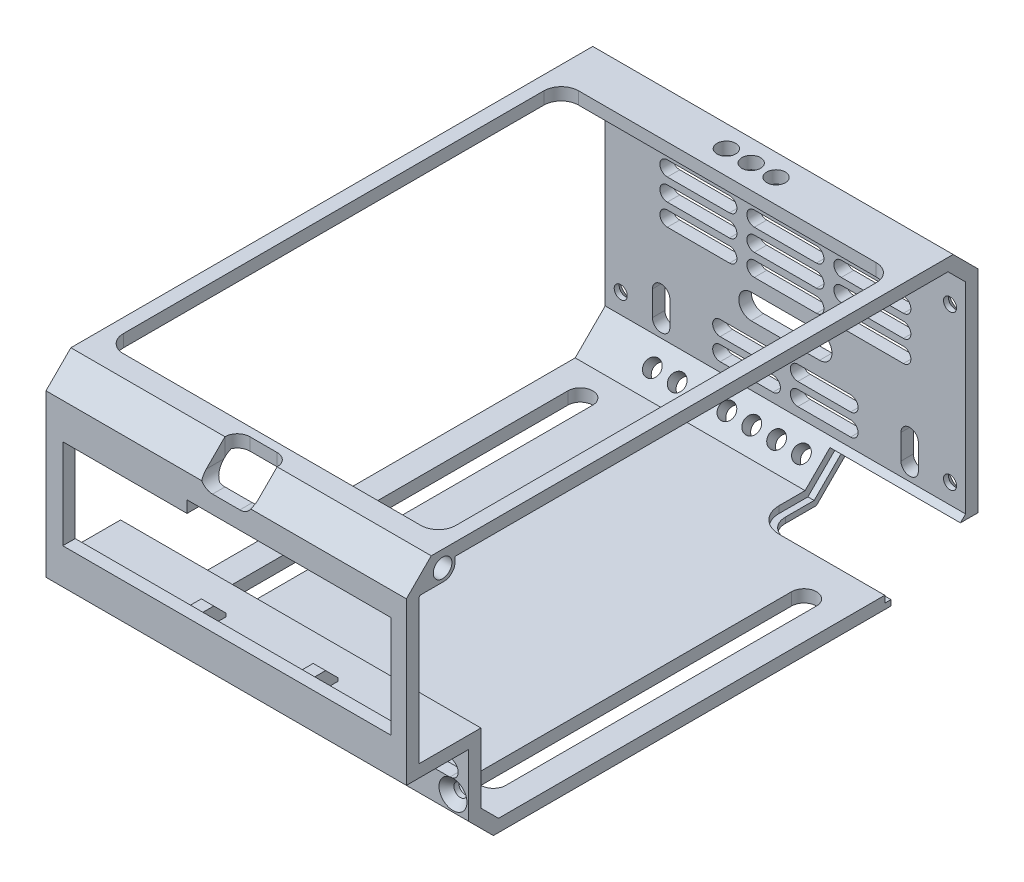
SolidWorks part; units mm, degrees
ref_plane "前视基准面" through (0, 0, 0) normal (0, 0, 1) x (1, 0, 0)
ref_plane "上视基准面" through (0, 0, 0) normal (0, 1, 0) x (1, 0, 0)
ref_plane "右视基准面" through (0, 0, 0) normal (1, 0, 0) x (0, 0, -1)
other "Configuration Table"
sketch "草图1" plane through (0, 0, 0) normal (0, 1, 0) x (1, 0, 0)
  line L1 (-28.831, 36.5169) -> (29.169, 36.5169)
  line L2 (-28.831, 36.5169) -> (-28.831, -55.4831)
  line L3 (-28.831, -55.4831) -> (29.169, -55.4831)
  line L4 (29.169, 36.5169) -> (29.169, -55.4831)
  dimension "D1" = 58
  dimension "D2" = 92
extrude "凸台-拉伸1" add sketch "草图1" along normal blind 44
sketch "草图2" plane through (-28.831, 0, 0) normal (-1, 0, 0) x (0, 0, 1)
  line L0 (55.4831, 44) -> (55.4831, 0) construction
  line L1 (55.4831, 14) -> (45.4831, 14)
  line L2 (55.4831, 14) -> (55.4831, 0)
  line L3 (55.4831, 0) -> (45.4831, 0)
  line L4 (45.4831, 14) -> (45.4831, 0)
  line L5 (-36.5169, 0) -> (55.4831, 0) construction
  dimension "D1" = 14
  dimension "D2" = 10
extrude "切除-拉伸1" cut sketch "草图2" against normal through all
chamfer "倒角1" distance 4 angle 45 3 edges at (0.169, 44, 55.4831) (0.169, 44, -36.5169) (0.169, 0, 45.4831)
chamfer "倒角2" distance 6 angle 45 1 edges at (0.169, 0, -36.5169)
sketch "草图3" plane through (-28.831, 0, 0) normal (-1, 0, 0) x (0, 0, 1)
  line L20 (-34.5169, 39.1716) -> (-34.5169, 6.8284)
  line L21 (-34.5169, 6.8284) -> (-29.6885, 2)
  line L22 (-29.6885, 2) -> (40.6547, 2)
  line L23 (40.6547, 2) -> (43.4831, 4.8284)
  line L24 (43.4831, 4.8284) -> (43.4831, 16)
  line L25 (43.4831, 16) -> (53.4831, 16)
  line L26 (53.4831, 16) -> (53.4831, 39.1716)
  line L27 (53.4831, 39.1716) -> (50.6547, 42)
  line L28 (50.6547, 42) -> (-31.6885, 42)
  line L29 (-31.6885, 42) -> (-34.5169, 39.1716)
  line L30 (-34.5169, 39.1716) -> (-34.5169, 6.8284)
  line L31 (-34.5169, 6.8284) -> (-29.6885, 2)
  line L32 (-29.6885, 2) -> (40.6547, 2)
  line L33 (40.6547, 2) -> (43.4831, 4.8284)
  line L34 (43.4831, 4.8284) -> (43.4831, 16)
  line L35 (43.4831, 16) -> (53.4831, 16)
  line L36 (53.4831, 16) -> (53.4831, 39.1716)
  line L37 (53.4831, 39.1716) -> (50.6547, 42)
  line L38 (50.6547, 42) -> (-31.6885, 42)
  line L39 (-31.6885, 42) -> (-34.5169, 39.1716)
  dimension "D1" = 2
extrude "切除-拉伸2" cut sketch "草图3" against normal through all
sketch "草图4" plane through (0, 0, 55.4831) normal (0, 0, 1) x (1, 0, 0)
  line L0 (26.669, 36.15) -> (-6.131, 36.15)
  line L2 (26.669, 36.15) -> (26.669, 19.75)
  line L3 (26.669, 19.75) -> (-26.131, 19.75)
  line L4 (-26.131, 34.25) -> (-26.131, 19.75)
  line L5 (-6.131, 36.15) -> (-6.131, 34.25)
  line L6 (-6.131, 34.25) -> (-26.131, 34.25)
  line L7 (29.169, 40) -> (29.169, 14) construction
  line L8 (-28.831, 44) -> (29.169, 44) construction
  dimension "D1" = 2.5
  dimension "D2" = 7.85
  dimension "D3" = 16.4
  dimension "D4" = 32.8
  dimension "D5" = 1.9
  dimension "D6" = 20
extrude "切除-拉伸3" cut sketch "草图4" against normal up to next
sketch "草图6" plane through (0, 44, 0) normal (0, 1, 0) x (1, 0, 0)
  line L0 (29.169, -51.4831) -> (29.169, 32.5169) construction
  line L1 (24.119, -48.0831) -> (-23.781, -48.0831)
  line L2 (26.919, -45.2831) -> (26.919, 22.3885)
  line L3 (24.119, 25.1885) -> (-23.781, 25.1885)
  line L4 (-26.581, -45.2831) -> (-26.581, 22.3885)
  line L5 (-28.831, 32.5169) -> (-28.831, -51.4831) construction
  line L6 (29.169, -55.4831) -> (-28.831, -55.4831) construction
  line L7 (29.169, 29.6885) -> (-28.831, 29.6885) construction
  arc A0 (-23.781, 25.1885) -> (-26.581, 22.3885) centre (-23.781, 22.3885) ccw
  arc A1 (-23.781, -48.0831) -> (-26.581, -45.2831) centre (-23.781, -45.2831) cw
  arc A2 (24.119, -48.0831) -> (26.919, -45.2831) centre (24.119, -45.2831) ccw
  arc A3 (26.919, 22.3885) -> (24.119, 25.1885) centre (24.119, 22.3885) ccw
  point P16 (-26.581, -48.0831)
  point P19 (26.919, -48.0831)
  point P22 (26.919, 25.1885)
  dimension "D5" = 2.8
  dimension "D1" = 2.25
  dimension "D2" = 2.25
  dimension "D3" = 7.4
  dimension "D4" = 4.5
extrude "切除-拉伸4" cut sketch "草图6" against normal up to next
sketch "草图7" plane through (0, 44, 0) normal (0, 1, 0) x (1, 0, 0)
  line L0 (29.169, -55.4831) -> (-28.831, -55.4831) construction
  line L1 (4.369, -55.4831) -> (-4.031, -55.4831)
  line L2 (4.369, -55.4831) -> (4.369, -49.4831)
  line L3 (4.369, -49.4831) -> (-4.031, -49.4831)
  line L4 (-4.031, -55.4831) -> (-4.031, -49.4831)
  point P6 (0.169, -55.4831)
  point P7 (0.169, -49.4831)
  dimension "D1" = 8.4
  dimension "D2" = 6
extrude "切除-拉伸5" cut sketch "草图7" against normal blind 5
fillet "圆角1" radius 2 4 edges at (-4.031, 39, 54.4831) (4.369, 39, 54.4831) (-4.031, 43, 49.4831) (4.369, 43, 49.4831)
sketch "草图8" plane through (0, 44, 0) normal (0, 1, 0) x (1, 0, 0)
  line L0 (-28.831, 36.5169) -> (29.169, 36.5169) construction
  circle A0 centre (4.169, 29.0169) radius 1.5
  circle A1 centre (0.169, 29.0169) radius 1.5
  circle A2 centre (-3.831, 29.0169) radius 1.5
  point P8 (0.169, 36.5169)
  dimension "D1" = 3
  dimension "D2" = 4
  dimension "D3" = 4
  dimension "D4" = 7.5
extrude "切除-拉伸6" cut sketch "草图8" against normal up to next
sketch "草图9" plane through (0, 16, 0) normal (0, 1, 0) x (1, 0, 0)
  line L0 (26.669, -53.4831) -> (-26.131, -53.4831) construction
  line L1 (11.169, -53.4831) -> (9.169, -53.4831)
  line L2 (11.169, -53.4831) -> (11.169, -48.4831)
  line L3 (11.169, -48.4831) -> (9.169, -48.4831)
  line L4 (9.169, -53.4831) -> (9.169, -48.4831)
  line L7 (-6.831, -53.4831) -> (-8.831, -53.4831)
  line L8 (-6.831, -53.4831) -> (-6.831, -48.4831)
  line L9 (-6.831, -48.4831) -> (-8.831, -48.4831)
  line L10 (-8.831, -53.4831) -> (-8.831, -48.4831)
  line L11 (29.169, -43.4831) -> (29.169, -53.4831) construction
  line L12 (-28.831, -43.4831) -> (-28.831, -53.4831) construction
  dimension "D1" = 2
  dimension "D2" = 2
  dimension "D3" = 18
  dimension "D4" = 20
  dimension "D5" = 5
extrude "凸台-拉伸2" add sketch "草图9" along normal blind 2.5
chamfer "倒角4" distance 2 angle 45 1 edges at (10.169, 18.5, 48.4831)
chamfer "倒角5" distance 2 angle 45 1 edges at (-7.831, 18.5, 48.4831)
sketch "草图10" plane through (0, 42, 0) normal (0, -1, 0) x (-1, 0, 0)
  line L0 (26.131, -53.4831) -> (6.131, -53.4831) construction
  line L1 (18.831, -53.4831) -> (20.831, -53.4831)
  line L2 (18.831, -53.4831) -> (18.831, -49.4831)
  line L3 (18.831, -49.4831) -> (20.831, -49.4831)
  line L4 (20.831, -53.4831) -> (20.831, -49.4831)
  line L5 (6.131, -53.4831) -> (-26.669, -53.4831) construction
  line L6 (-21.169, -53.4831) -> (-19.169, -53.4831)
  line L7 (-21.169, -53.4831) -> (-21.169, -49.4831)
  line L8 (-21.169, -49.4831) -> (-19.169, -49.4831)
  line L9 (-19.169, -53.4831) -> (-19.169, -49.4831)
  line L10 (-29.169, 34.5169) -> (28.831, 34.5169) construction
  line L11 (-13.169, 34.5169) -> (-11.169, 34.5169)
  line L12 (-13.169, 34.5169) -> (-13.169, 29.5169)
  line L13 (-13.169, 29.5169) -> (-11.169, 29.5169)
  line L14 (-11.169, 34.5169) -> (-11.169, 29.5169)
  line L15 (-29.169, -50.6547) -> (-29.169, 31.6885) construction
  line L16 (10.831, 34.5169) -> (12.831, 34.5169)
  line L17 (10.831, 34.5169) -> (10.831, 29.5169)
  line L18 (10.831, 29.5169) -> (12.831, 29.5169)
  line L19 (12.831, 34.5169) -> (12.831, 29.5169)
  line L20 (28.831, -50.6547) -> (28.831, 31.6885) construction
  dimension "D1" = 2
  dimension "D2" = 8
  dimension "D3" = 8
  dimension "D4" = 16
  dimension "D5" = 16
  dimension "D6" = 4
  dimension "D7" = 5
extrude "凸台-拉伸3" add sketch "草图10" along normal blind 2.6
sketch "草图11" plane through (0, 0, 45.4831) normal (0, 0, 1) x (1, 0, 0)
  line L0 (26.169, 10) -> (-25.831, 10) construction
  line L1 (26.169, 8.66) -> (-25.831, 8.66)
  line L2 (26.169, 11.34) -> (-25.831, 11.34)
  line L3 (29.169, 0) -> (-28.831, 0) construction
  line L4 (-28.831, 0) -> (-28.831, 4) construction
  line L5 (29.169, 4) -> (29.169, 0) construction
  arc A0 (26.169, 8.66) -> (26.169, 11.34) centre (26.169, 10) ccw
  arc A1 (-25.831, 11.34) -> (-25.831, 8.66) centre (-25.831, 10) ccw
  point P2 (0.169, 10)
  dimension "D4" = 1.34
  dimension "D1" = 10
  dimension "D2" = 3
  dimension "D3" = 3
extrude "切除-拉伸7" cut sketch "草图11" against normal up to next
sketch "草图12" plane through (0, 0, 45.4831) normal (0, 0, 1) x (1, 0, 0)
  line L0 (26.169, 11.34) -> (-25.831, 11.34) construction
  line L1 (-23.881, 11.34) -> (-20.431, 11.34)
  line L2 (-23.881, 11.34) -> (-23.881, 13.34)
  line L3 (-23.881, 13.34) -> (-20.431, 13.34)
  line L4 (-20.431, 11.34) -> (-20.431, 13.34)
  line L5 (-23.881, 13.34) -> (-23.881, 11.34) construction
  line L6 (-26.831, 13.34) -> (-4.831, 13.34) construction
  line L7 (-9.881, 13.34) -> (-9.881, 11.34) construction
  line L8 (-9.881, 11.34) -> (-6.431, 11.34)
  line L9 (-9.881, 11.34) -> (-9.881, 13.34)
  line L10 (-9.881, 13.34) -> (-6.431, 13.34)
  line L11 (-6.431, 11.34) -> (-6.431, 13.34)
  dimension "D1" = 3.45
  dimension "D2" = 3.45
extrude "切除-拉伸8" cut sketch "草图12" against normal up to next
sketch "草图13" plane through (0, 38.2584, -38.2584) normal (0, 0.7071, -0.7071) x (1, 0, 0)
  line L0 (6.169, -5.4629) -> (-5.831, -5.4629) construction
  line L1 (6.169, -6.6629) -> (-5.831, -6.6629)
  line L2 (6.169, -4.2629) -> (-5.831, -4.2629)
  line L3 (-28.831, -2.4629) -> (29.169, -2.4629) construction
  arc A0 (6.169, -6.6629) -> (6.169, -4.2629) centre (6.169, -5.4629) ccw
  arc A1 (-5.831, -4.2629) -> (-5.831, -6.6629) centre (-5.831, -5.4629) ccw
  point P2 (0.169, -5.4629)
  point P9 (0.169, -2.4629)
  dimension "D1" = 1.2
  dimension "D2" = 3
  dimension "D3" = 12
extrude "切除-拉伸9" cut sketch "草图13" against normal up to next
sketch "草图14" plane through (0, 0, -36.5169) normal (0, 0, -1) x (-1, 0, 0)
  line L0 (-5.669, 18.5) -> (5.331, 18.5) construction
  line L1 (-5.669, 20.5) -> (5.331, 20.5)
  line L2 (-5.669, 16.5) -> (5.331, 16.5)
  line L3 (28.831, 0) -> (-29.169, 0) construction
  arc A0 (-5.669, 20.5) -> (-5.669, 16.5) centre (-5.669, 18.5) ccw
  arc A1 (5.331, 16.5) -> (5.331, 20.5) centre (5.331, 18.5) ccw
  point P2 (-0.169, 18.5)
  point P9 (-0.169, 0)
  dimension "D1" = 2
  dimension "D2" = 11
  dimension "D3" = 18.5
extrude "切除-拉伸10" cut sketch "草图14" against normal up to next
sketch "草图15" plane through (0, 0, -36.5169) normal (0, 0, -1) x (-1, 0, 0)
  line L0 (-9.169, 38) -> (-19.169, 38) construction
  line L1 (-9.169, 36.8) -> (-19.169, 36.8)
  line L2 (-9.169, 39.2) -> (-19.169, 39.2)
  line L3 (28.831, 0) -> (-29.169, 0) construction
  line L4 (-29.169, 44) -> (28.831, 44) construction
  line L5 (4.831, 38) -> (-5.169, 38) construction
  line L6 (4.831, 36.8) -> (-5.169, 36.8)
  line L7 (4.831, 39.2) -> (-5.169, 39.2)
  line L8 (28.831, 44) -> (28.831, 40) construction
  line L11 (4.831, 34.5) -> (-5.169, 34.5) construction
  line L12 (4.831, 33.3) -> (-5.169, 33.3)
  line L13 (4.831, 35.7) -> (-5.169, 35.7)
  line L17 (4.831, 31) -> (-5.169, 31) construction
  line L18 (4.831, 29.8) -> (-5.169, 29.8)
  line L19 (4.831, 32.2) -> (-5.169, 32.2)
  line L20 (18.831, 31) -> (8.831, 31) construction
  line L21 (18.831, 29.8) -> (8.831, 29.8)
  line L22 (18.831, 32.2) -> (8.831, 32.2)
  line L23 (4.831, 27.5) -> (-5.169, 27.5) construction
  line L24 (4.831, 26.3) -> (-5.169, 26.3)
  line L25 (4.831, 28.7) -> (-5.169, 28.7)
  line L26 (18.831, 27.5) -> (8.831, 27.5) construction
  line L27 (18.831, 26.3) -> (8.831, 26.3)
  line L28 (18.831, 28.7) -> (8.831, 28.7)
  line L29 (4.831, 24) -> (-5.169, 24) construction
  line L30 (4.831, 22.8) -> (-5.169, 22.8)
  line L31 (4.831, 25.2) -> (-5.169, 25.2)
  line L32 (18.831, 24) -> (8.831, 24) construction
  line L33 (18.831, 22.8) -> (8.831, 22.8)
  line L34 (18.831, 25.2) -> (8.831, 25.2)
  line L35 (-9.169, 34.5) -> (-19.169, 34.5) construction
  line L36 (-9.169, 33.3) -> (-19.169, 33.3)
  line L37 (-9.169, 35.7) -> (-19.169, 35.7)
  line L38 (-9.169, 31) -> (-19.169, 31) construction
  line L39 (-9.169, 29.8) -> (-19.169, 29.8)
  line L40 (-9.169, 32.2) -> (-19.169, 32.2)
  line L41 (-9.169, 27.5) -> (-19.169, 27.5) construction
  line L42 (-9.169, 26.3) -> (-19.169, 26.3)
  line L43 (-9.169, 28.7) -> (-19.169, 28.7)
  line L44 (-9.169, 24) -> (-19.169, 24) construction
  line L45 (-9.169, 22.8) -> (-19.169, 22.8)
  line L46 (-9.169, 25.2) -> (-19.169, 25.2)
  line L47 (-20.169, 13) -> (-20.169, 9) construction
  line L50 (-18.769, 13) -> (-18.769, 9)
  line L53 (-21.569, 13) -> (-21.569, 9)
  line L56 (19.831, 13) -> (19.831, 9) construction
  line L65 (-0.169, -2.58) -> (-0.169, -9.8045) construction
  line L66 (-10.669, 13) -> (-2.169, 13) construction
  line L67 (-29.169, 6) -> (28.831, 6) construction
  line L68 (18.431, 13) -> (18.431, 9)
  line L69 (21.231, 13) -> (21.231, 9)
  line L70 (-10.669, 14.2) -> (-2.169, 14.2)
  line L71 (-10.669, 11.8) -> (-2.169, 11.8)
  line L72 (-10.669, 9.5) -> (-2.169, 9.5) construction
  line L73 (-10.669, 10.7) -> (-2.169, 10.7)
  line L74 (-10.669, 8.3) -> (-2.169, 8.3)
  line L75 (10.331, 13) -> (1.831, 13) construction
  line L76 (10.331, 14.2) -> (1.831, 14.2)
  line L77 (10.331, 11.8) -> (1.831, 11.8)
  line L78 (10.331, 9.5) -> (1.831, 9.5) construction
  line L79 (10.331, 10.7) -> (1.831, 10.7)
  line L80 (10.331, 8.3) -> (1.831, 8.3)
  line L81 (28.831, 40) -> (28.831, 6) construction
  line L86 (9.831, 39.2) -> (21.831, 39.2)
  line L87 (8.831, 38.2) -> (8.831, 34.3)
  line L88 (9.831, 33.3) -> (21.831, 33.3)
  line L89 (22.831, 38.2) -> (22.831, 34.3)
  line L174 (18.831, 34.5) -> (8.831, 34.5) construction
  line L175 (18.831, 33.3) -> (8.831, 33.3)
  line L176 (18.831, 35.7) -> (8.831, 35.7)
  line L177 (18.831, 38) -> (8.831, 38) construction
  line L178 (18.831, 36.8) -> (8.831, 36.8)
  line L179 (18.831, 39.2) -> (8.831, 39.2)
  line L180 (18.831, 34.5) -> (8.831, 34.5) construction
  line L181 (18.831, 33.3) -> (8.831, 33.3)
  line L182 (18.831, 35.7) -> (8.831, 35.7)
  line L183 (18.831, 38) -> (8.831, 38) construction
  line L184 (18.831, 36.8) -> (8.831, 36.8)
  line L185 (18.831, 39.2) -> (8.831, 39.2)
  arc A0 (-9.169, 36.8) -> (-9.169, 39.2) centre (-9.169, 38) ccw
  arc A1 (-19.169, 39.2) -> (-19.169, 36.8) centre (-19.169, 38) ccw
  arc A2 (4.831, 36.8) -> (4.831, 39.2) centre (4.831, 38) ccw
  arc A3 (-5.169, 39.2) -> (-5.169, 36.8) centre (-5.169, 38) ccw
  arc A6 (4.831, 33.3) -> (4.831, 35.7) centre (4.831, 34.5) ccw
  arc A7 (-5.169, 35.7) -> (-5.169, 33.3) centre (-5.169, 34.5) ccw
  arc A10 (4.831, 29.8) -> (4.831, 32.2) centre (4.831, 31) ccw
  arc A11 (-5.169, 32.2) -> (-5.169, 29.8) centre (-5.169, 31) ccw
  arc A12 (18.831, 29.8) -> (18.831, 32.2) centre (18.831, 31) ccw
  arc A13 (8.831, 32.2) -> (8.831, 29.8) centre (8.831, 31) ccw
  arc A14 (4.831, 26.3) -> (4.831, 28.7) centre (4.831, 27.5) ccw
  arc A15 (-5.169, 28.7) -> (-5.169, 26.3) centre (-5.169, 27.5) ccw
  arc A16 (18.831, 26.3) -> (18.831, 28.7) centre (18.831, 27.5) ccw
  arc A17 (8.831, 28.7) -> (8.831, 26.3) centre (8.831, 27.5) ccw
  arc A18 (4.831, 22.8) -> (4.831, 25.2) centre (4.831, 24) ccw
  arc A19 (-5.169, 25.2) -> (-5.169, 22.8) centre (-5.169, 24) ccw
  arc A20 (18.831, 22.8) -> (18.831, 25.2) centre (18.831, 24) ccw
  arc A21 (8.831, 25.2) -> (8.831, 22.8) centre (8.831, 24) ccw
  arc A22 (-9.169, 33.3) -> (-9.169, 35.7) centre (-9.169, 34.5) ccw
  arc A23 (-19.169, 35.7) -> (-19.169, 33.3) centre (-19.169, 34.5) ccw
  arc A24 (-9.169, 29.8) -> (-9.169, 32.2) centre (-9.169, 31) ccw
  arc A25 (-19.169, 32.2) -> (-19.169, 29.8) centre (-19.169, 31) ccw
  arc A26 (-9.169, 26.3) -> (-9.169, 28.7) centre (-9.169, 27.5) ccw
  arc A27 (-19.169, 28.7) -> (-19.169, 26.3) centre (-19.169, 27.5) ccw
  arc A28 (-9.169, 22.8) -> (-9.169, 25.2) centre (-9.169, 24) ccw
  arc A29 (-19.169, 25.2) -> (-19.169, 22.8) centre (-19.169, 24) ccw
  arc A42 (-18.769, 13) -> (-21.569, 13) centre (-20.169, 13) ccw
  arc A43 (-21.569, 9) -> (-18.769, 9) centre (-20.169, 9) ccw
  arc A46 (18.431, 13) -> (21.231, 13) centre (19.831, 13) cw
  arc A47 (21.231, 9) -> (18.431, 9) centre (19.831, 9) cw
  arc A48 (-10.669, 14.2) -> (-10.669, 11.8) centre (-10.669, 13) ccw
  arc A49 (-2.169, 11.8) -> (-2.169, 14.2) centre (-2.169, 13) ccw
  arc A50 (-10.669, 10.7) -> (-10.669, 8.3) centre (-10.669, 9.5) ccw
  arc A51 (-2.169, 8.3) -> (-2.169, 10.7) centre (-2.169, 9.5) ccw
  arc A52 (10.331, 14.2) -> (10.331, 11.8) centre (10.331, 13) cw
  arc A53 (1.831, 11.8) -> (1.831, 14.2) centre (1.831, 13) cw
  arc A54 (10.331, 10.7) -> (10.331, 8.3) centre (10.331, 9.5) cw
  arc A55 (1.831, 8.3) -> (1.831, 10.7) centre (1.831, 9.5) cw
  arc A60 (21.831, 33.3) -> (22.831, 34.3) centre (21.831, 34.3) ccw
  arc A61 (21.831, 39.2) -> (22.831, 38.2) centre (21.831, 38.2) cw
  arc A62 (9.831, 39.2) -> (8.831, 38.2) centre (9.831, 38.2) ccw
  arc A63 (8.831, 34.3) -> (9.831, 33.3) centre (9.831, 34.3) ccw
  arc A124 (18.831, 33.3) -> (18.831, 35.7) centre (18.831, 34.5) ccw
  arc A125 (8.831, 35.7) -> (8.831, 33.3) centre (8.831, 34.5) ccw
  arc A126 (18.831, 36.8) -> (18.831, 39.2) centre (18.831, 38) ccw
  arc A127 (8.831, 39.2) -> (8.831, 36.8) centre (8.831, 38) ccw
  point P2 (-14.169, 38)
  point P9 (-0.169, 0)
  point P14 (-20.169, 11)
  point P17 (-0.169, 38)
  point P24 (13.831, 34.5)
  point P31 (-0.169, 34.5)
  point P45 (-0.169, 31)
  point P52 (13.831, 31)
  point P59 (-0.169, 27.5)
  point P66 (13.831, 27.5)
  point P73 (-0.169, 24)
  point P80 (13.831, 24)
  point P87 (-14.169, 34.5)
  point P94 (-14.169, 31)
  point P101 (-14.169, 27.5)
  point P108 (-14.169, 24)
  point P119 (19.831, 11)
  point P130 (-6.419, 13)
  point P138 (-6.419, 9.5)
  point P144 (6.081, 13)
  point P151 (6.081, 9.5)
  point P158 (13.831, 38)
  point P165 (22.831, 39.2)
  point P168 (8.831, 39.2)
  point P171 (8.831, 33.3)
  point P174 (13.831, 34.5)
  point P181 (13.831, 38)
  point P188 (13.831, 34.5)
  point P195 (13.831, 38)
  point P203 (13.831, 34.5)
  point P210 (13.831, 38)
  point P217 (13.831, 34.5)
  point P224 (13.831, 38)
  point P231 (13.831, 34.5)
  point P238 (13.831, 38)
  point P245 (13.831, 34.5)
  point P252 (13.831, 38)
  point P259 (13.831, 34.5)
  point P266 (13.831, 38)
  point P273 (13.831, 34.5)
  point P280 (13.831, 38)
  point P287 (13.831, 34.5)
  point P294 (13.831, 38)
  point P301 (13.831, 34.5)
  point P308 (13.831, 38)
  point P315 (13.831, 34.5)
  point P322 (13.831, 38)
  point P329 (13.831, 34.5)
  point P336 (13.831, 38)
  point P343 (13.831, 34.5)
  point P350 (13.831, 38)
  point P357 (13.831, 34.5)
  point P364 (13.831, 38)
  point P371 (13.831, 34.5)
  point P378 (13.831, 38)
  point P385 (13.831, 34.5)
  point P392 (13.831, 38)
  dimension "D1" = 1.2
  dimension "D6" = 1.4
  dimension "D10" = 1.2
  dimension "D16" = 1
  dimension "D2" = 10
  dimension "D3" = 6
  dimension "D7" = 5
  dimension "D8" = 20
  dimension "D9" = 4
  dimension "D11" = 8.5
  dimension "D12" = 2
  dimension "D13" = 7
  dimension "D14" = 2
  dimension "D15" = 6
  dimension "D17" = 20
  dimension "D4" = 3
  dimension "D5" = 5
extrude "切除-拉伸11" cut sketch "草图15" against normal up to next
sketch "草图17" plane through (0, -15.2584, -15.2584) normal (0, -0.7071, -0.7071) x (1, 0, 0)
  line L0 (29.169, -21.5787) -> (29.169, -30.064) construction
  line L2 (-28.831, -30.064) -> (-28.831, -21.5787) construction
  circle A0 centre (5.169, -25.8213) radius 1.3
  circle A1 centre (1.169, -25.8213) radius 1.3
  circle A2 centre (-2.831, -25.8213) radius 1.3
  circle A3 centre (-6.831, -25.8213) radius 1.3
  circle A4 centre (-10.831, -25.8213) radius 1.3
  circle A5 centre (-14.831, -25.8213) radius 1.3
  circle A6 centre (-18.831, -25.8213) radius 1.3
  point P4 (29.169, -25.8213)
  dimension "D1" = 2.6
  dimension "D3" = 10
  dimension "D2" = 7
extrude "切除-拉伸12" cut sketch "草图17" against normal up to next
sketch "草图18" plane through (0, 0, 0) normal (0, -1, 0) x (1, 0, 0)
  line L0 (23.169, 35.4831) -> (23.169, -14.5169) construction
  line L1 (25.169, 35.4831) -> (25.169, -14.5169)
  line L2 (21.169, 35.4831) -> (21.169, -14.5169)
  line L3 (-22.831, 35.4831) -> (-22.831, -24.5169) construction
  line L4 (-20.831, 35.4831) -> (-20.831, -24.5169)
  line L5 (-24.831, 35.4831) -> (-24.831, -24.5169)
  line L6 (29.169, 41.4831) -> (-28.831, 41.4831) construction
  line L7 (29.169, 41.4831) -> (29.169, -30.5169) construction
  line L8 (-28.831, -30.5169) -> (29.169, -30.5169) construction
  line L9 (-28.831, -30.5169) -> (-28.831, 41.4831) construction
  arc A0 (25.169, 35.4831) -> (21.169, 35.4831) centre (23.169, 35.4831) ccw
  arc A1 (21.169, -14.5169) -> (25.169, -14.5169) centre (23.169, -14.5169) ccw
  arc A2 (-20.831, 35.4831) -> (-24.831, 35.4831) centre (-22.831, 35.4831) ccw
  arc A3 (-24.831, -24.5169) -> (-20.831, -24.5169) centre (-22.831, -24.5169) ccw
  point P2 (23.169, 10.4831)
  point P9 (-22.831, 5.4831)
  dimension "D7" = 2
  dimension "D8" = 2
  dimension "D1" = 6
  dimension "D2" = 6
  dimension "D3" = 16
  dimension "D4" = 6
  dimension "D5" = 6
  dimension "D6" = 6
extrude "切除-拉伸13" cut sketch "草图18" against normal up to next
sketch "草图19" plane through (0, 0, -36.5169) normal (0, 0, -1) x (-1, 0, 0)
  line L0 (-29.169, 6) -> (-29.169, 40) construction
  line L1 (28.831, 40) -> (-29.169, 40) construction
  line L2 (28.831, 44) -> (28.831, 40) construction
  line L3 (-29.169, 6) -> (28.831, 6) construction
  circle A0 centre (-26.669, 34.8) radius 1.05
  circle A1 centre (26.331, 34.8) radius 1.05
  circle A2 centre (-26.669, 10) radius 1.05
  circle A3 centre (26.331, 10) radius 1.05
  dimension "D1" = 2.1
  dimension "D2" = 2.5
  dimension "D3" = 5.2
  dimension "D4" = 2.5
  dimension "D5" = 4
extrude "切除-拉伸14" cut sketch "草图19" against normal up to next
sketch "草图20" plane through (0, 0, 45.4831) normal (0, 0, 1) x (1, 0, 0)
  line L0 (-28.831, 4) -> (29.169, 4) construction
  line L2 (29.169, 14) -> (29.169, 4) construction
  line L3 (-28.831, 14) -> (-28.831, 4) construction
  circle A0 centre (26.669, 6.5) radius 1.05
  circle A1 centre (-26.331, 6.5) radius 1.05
  dimension "D1" = 2.1
  dimension "D2" = 2.5
  dimension "D3" = 2.5
  dimension "D4" = 2.5
extrude "切除-拉伸15" cut sketch "草图20" against normal up to next
chamfer "倒角6" distance 1.2 angle 45 6 edges at (27.719, 6.5, 45.4831) (-25.281, 6.5, 45.4831) (-27.381, 34.8, -36.5169) (-27.381, 10, -36.5169) (25.619, 10, -36.5169) (25.619, 34.8, -36.5169)
sketch "草图21" plane through (29.169, 0, 0) normal (1, 0, 0) x (0, 0, -1)
  line L8 (-47.6547, 42) -> (-50.6547, 42)
  line L9 (-50.6547, 42) -> (-53.2547, 39.4)
  line L10 (-53.2547, 39.4) -> (-47.6547, 39.4)
  line L11 (-47.6547, 39.4) -> (-47.6547, 42)
  dimension "D1" = 3
extrude "凸台-拉伸4" add sketch "草图21" against normal blind 2.5
sketch "草图22" plane through (-28.831, 0, 0) normal (-1, 0, 0) x (0, 0, 1)
  line L4 (50.6547, 42) -> (47.6547, 42)
  line L5 (53.2547, 39.4) -> (50.6547, 42)
  line L6 (47.6547, 39.4) -> (53.2547, 39.4)
  line L7 (47.6547, 42) -> (47.6547, 39.4)
  line L8 (50.6547, 42) -> (47.6547, 42)
  line L9 (53.2547, 39.4) -> (50.6547, 42)
  line L10 (47.6547, 39.4) -> (53.2547, 39.4)
  line L11 (47.6547, 42) -> (47.6547, 39.4)
  dimension "D1" = 0
extrude "凸台-拉伸5" add sketch "草图22" against normal blind 2.5
sketch "草图23" plane through (-28.831, 0, 0) normal (-1, 0, 0) x (0, 0, 1)
  line L1 (47.6547, 42) -> (47.6547, 39.4) construction
  line L3 (47.6547, 39.4) -> (53.2547, 39.4) construction
  circle A0 centre (49.6547, 41.4) radius 1.5
  dimension "D1" = 3
  dimension "D2" = 2
  dimension "D3" = 2
extrude "切除-拉伸16" cut sketch "草图23" against normal blind 2.5
sketch "草图24" plane through (29.169, 0, 0) normal (1, 0, 0) x (0, 0, -1)
  circle A1 centre (-49.6547, 41.4) radius 1.5
  circle A2 centre (-49.6547, 41.4) radius 1.5
  dimension "D1" = 0
extrude "切除-拉伸17" cut sketch "草图24" against normal blind 2.5
fillet "圆角3" radius 1.8 2 edges at (-27.581, 39.4, 47.6547) (27.919, 39.4, 47.6547)
sketch "草图25" plane through (29.169, 0, 0) normal (1, 0, 0) x (0, 0, -1)
  line L1 (36.5169, 6) -> (21.5169, 6)
  line L2 (36.5169, 6) -> (36.5169, -2)
  line L3 (36.5169, -2) -> (21.5169, -2)
  line L4 (21.5169, 6) -> (21.5169, -2)
  dimension "D1" = 15
  dimension "D2" = 8
extrude "切除-拉伸18" cut sketch "草图25" against normal blind 21
sketch "草图27" plane through (8.169, 0, 0) normal (1, 0, 0) x (0, 0, -1)
  line L2 (36.5169, 6) -> (33.6885, 6) construction
  line L3 (30.5169, 0) -> (21.5169, 0) construction
  line L4 (21.5169, 0.9) -> (30.1441, 0.9)
  line L5 (30.1441, 0.9) -> (35.8805, 6.6364)
  line L6 (21.5169, 0.9) -> (30.1441, 0.9)
  line L7 (30.1441, 0.9) -> (35.2441, 6)
  line L8 (30.5169, 0) -> (36.5169, 6) construction
  line L9 (30.5169, 0) -> (21.5169, 0)
  line L10 (30.5169, 0) -> (36.5169, 6)
  line L11 (36.5169, 6) -> (35.2441, 6)
  line L12 (21.5169, 0) -> (21.5169, 0.9)
  dimension "D1" = 0.9
extrude "凸台-拉伸7" add sketch "草图27" along normal blind 1
sketch "草图28" plane through (0, 0, -21.5169) normal (0, 0, -1) x (-1, 0, 0)
  line L1 (-9.169, 0.9) -> (-29.169, 0.9)
  line L2 (-9.169, 0.9) -> (-9.169, 0)
  line L3 (-9.169, 0) -> (-29.169, 0)
  line L4 (-29.169, 0.9) -> (-29.169, 0)
extrude "凸台-拉伸8" add sketch "草图28" along normal blind 1
fillet "圆角4" radius 3 1 edges at (9.169, 0.45, -22.5169)
fillet "圆角5" radius 4 1 edges at (8.169, 1.45, -21.5169)
